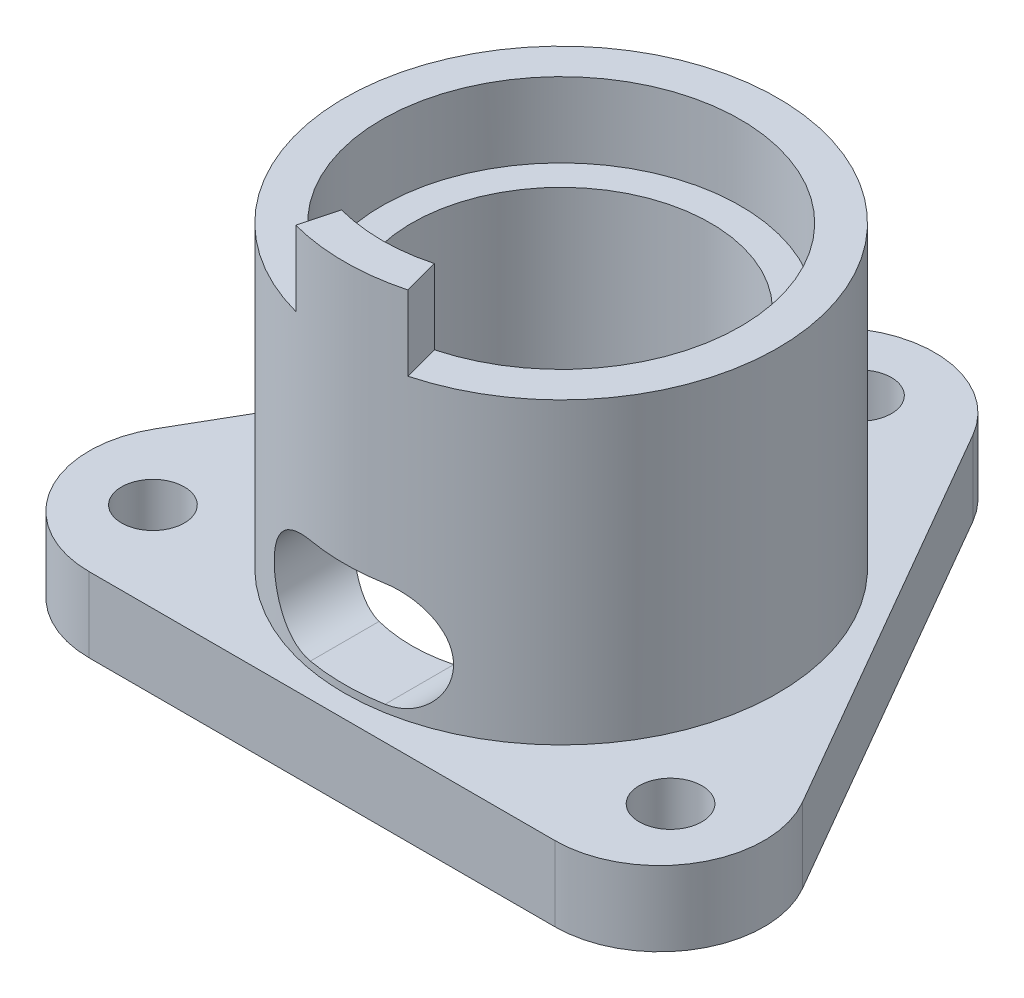
SolidWorks part; units mm, degrees
material "6061 Alloy"
ref_plane "Front Plane" through (0, 0, 0) normal (0, 0, 1) x (1, 0, 0)
ref_plane "Top Plane" through (0, 0, 0) normal (0, 1, 0) x (1, 0, 0)
ref_plane "Right Plane" through (0, 0, 0) normal (1, 0, 0) x (0, 0, -1)
sketch "Sketch1" plane through (0, 0, 0) normal (0, 1, 0) x (1, 0, 0)
  circle A0 centre (0, 0) radius 10
  circle A1 centre (0, 0) radius 14.5
  dimension "D1" = 29
  dimension "D2" = 20
extrude "Boss-Extrude1" add sketch "Sketch1" along normal mid plane 15
sketch "Sketch2" plane through (0, 7.5, 0) normal (0, 1, 0) x (1, 0, 0)
  circle A0 centre (0, 0) radius 14.5
  circle A1 centre (0, 0) radius 12
  dimension "D1" = 29
  dimension "D2" = 24
extrude "Boss-Extrude2" add sketch "Sketch2" along normal blind 5
sketch "Sketch3" plane through (0, -7.5, 0) normal (0, -1, 0) x (-1, 0, 0)
  line L0 (0, 0) -> (0, 38.6793) construction
  line L1 (0, 0) -> (-32.5079, 0) construction
  line L2 (0, 32) -> (-27.7128, -16)
  line L3 (-27.7128, -16) -> (27.7128, -16)
  line L4 (0, 32) -> (27.7128, -16)
  line L5 (0, 0) -> (27.7128, -16) construction
  circle A0 centre (0, 0) radius 12
  circle A1 centre (17.3205, -10) radius 2.1
  circle A2 centre (-17.3205, -10) radius 2.1
  circle A3 centre (0, 20) radius 2.1
  point P9 (0, -16)
  point P18 (0, 0)
  dimension "D1" = 24
  dimension "D4" = 20
  dimension "D5" = 4.2
  dimension "D2" = 120
  dimension "D3" = 16
  dimension "D6" = 3
extrude "Boss-Extrude3" add sketch "Sketch3" along normal blind 5
fillet "Fillet1" radius 7 3 edges at (-27.7128, -10, 16) (27.7128, -10, 16) (0, -10, -32)
sketch "Sketch4" plane through (0, 12.5, 0) normal (0, 1, 0) x (1, 0, 0)
  line L0 (0, 0) -> (0, -47.2539) construction
  line L1 (0, 0) -> (7.9041, -29.4985) construction
  line L2 (3.1058, -11.5911) -> (3.7529, -14.0059)
  line L3 (-3.1058, -11.5911) -> (-3.7529, -14.0059)
  circle A0 centre (0, 0) radius 12
  circle A1 centre (0, 0) radius 14.5
  circle M4 centre (0, 0) radius 14.5
  circle M5 centre (0, 0) radius 12
  dimension "D1" = 24
  dimension "D2" = 29
  dimension "D3" = 15
extrude "Boss-Extrude4" add sketch "Sketch4" along normal blind 5 contours L3 L2 M5 M4 region at (0, 12.5, 13.138)
sketch "Sketch5" plane through (0, 0, 0) normal (0, 0, 1) x (1, 0, 0)
  line L0 (0, 0) -> (0, -21.4052) construction
  line L1 (-2.5, -3.5) -> (2.5, -3.5) construction
  line L2 (-2.5, 0) -> (2.5, 0)
  line L3 (-2.5, -7) -> (2.5, -7)
  line L4 (15.5885, -12.5) -> (22.5885, -12.5) construction
  arc A0 (-2.5, 0) -> (-2.5, -7) centre (-2.5, -3.5) ccw
  arc A1 (2.5, -7) -> (2.5, 0) centre (2.5, -3.5) ccw
  point P5 (0, -3.5)
  dimension "D2" = 3.5
  dimension "D1" = 5
  dimension "D3" = 9
extrude "Cut-Extrude1" cut sketch "Sketch5" along normal through all
fillet "Fillet2" [suppressed] radius 2
